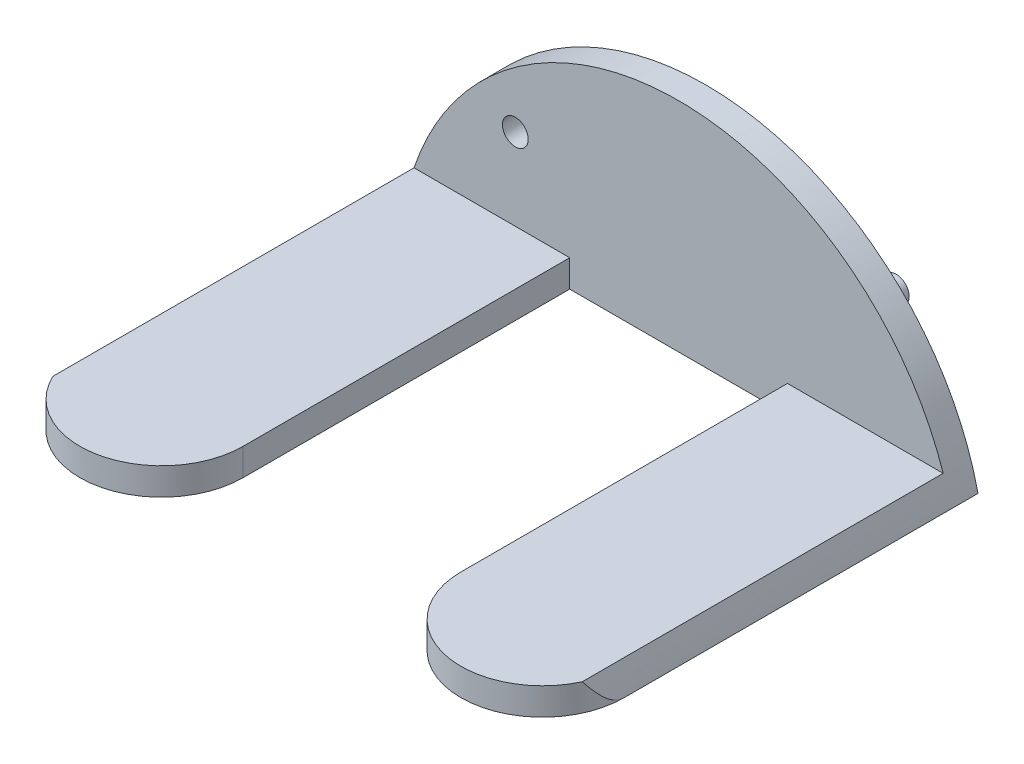
SolidWorks part; units mm, degrees
ref_plane "Front Plane" through (0, 0, 0) normal (0, 0, 1) x (1, 0, 0)
ref_plane "Top Plane" through (0, 0, 0) normal (0, 1, 0) x (1, 0, 0)
ref_plane "Right Plane" through (0, 0, 0) normal (1, 0, 0) x (0, 0, -1)
sketch "Sketch2" plane through (0, 0, 0) normal (1, 0, 0) x (0, 0, -1)
  line L0 (-50.8, 0) -> (0, 0)
  line L1 (0, 0) -> (0, 25.4)
  line L3 (-3.175, 25.4) -> (-3.175, 3.175)
  line L4 (-3.175, 3.175) -> (-50.8, 3.175)
  line L6 (-3.175, 25.4) -> (0, 25.4)
  line L7 (-50.8, 3.175) -> (-50.8, 0)
  dimension "D1" = 3.175
  dimension "D2" = 3.175
  dimension "D3" = 25.4
  dimension "D4" = 50.8
extrude "Boss-Extrude1" add sketch "Sketch2" along normal blind 63.5
sketch "Sketch3" plane through (0, 0, 0) normal (0, 0, -1) x (-1, 0, 0)
  line L0 (-50.8, 12.7) -> (-12.7, 12.7) construction
  line L1 (-63.5, 0) -> (0, 0) construction
  circle A0 centre (-50.8, 12.7) radius 1.5
  circle A1 centre (-12.7, 12.7) radius 1.5
  point P4 (-31.75, 12.7)
  point P7 (-31.75, 0)
  dimension "D3" = 3
  dimension "D1" = 12.7
  dimension "D2" = 38.1
extrude "Cut-Extrude1" cut sketch "Sketch3" against normal through all contours A1 | A1 region at (12.7, 12.7, 0)
extrude "Boss-Extrude2" add sketch "Sketch3<3>" along normal blind 3.175 contours A0 region at (50.8, 12.7, 0)
sketch "Sketch3<3>" plane through (0, 0, 0) normal (0, 0, -1) x (-1, 0, 0) same geometry as "Sketch3"
sketch "Sketch4" plane through (0, 0, 0) normal (0, 0, -1) x (-1, 0, 0)
  line L0 (-63.5, 0) -> (-63.5, 25.4)
  line L3 (-63.5, 25.4) -> (0, 25.4)
  line L4 (0, 25.4) -> (0, 0)
  line L5 (0, 0) -> (-63.5, 0)
  arc A0 (0, 0) -> (-63.5, 0) centre (-31.75, -7.1438) ccw
  line M7 (0, 0) -> (0, 25.4)
  line M9 (-63.5, 25.4) -> (-63.5, 0)
extrude "Cut-Extrude2" cut sketch "Sketch4" against normal through all contours M9 | L3 L0 | M7 | L3 L4 region at (56.285, 18.8467, 0) region at (7.215, 18.8467, 0)
sketch "Sketch5" plane through (0, 3.175, 0) normal (0, 1, 0) x (1, 0, 0)
  line L0 (0, -3.175) -> (63.5, -3.175)
  line L1 (63.5, -50.8) -> (63.5, 0) construction
  line L2 (0, -50.8) -> (0, 0) construction
  line L3 (0.8855, -3.175) -> (62.6145, -3.175) construction
  line L4 (0, -3.175) -> (0, -50.8)
  line L5 (0, -50.8) -> (63.5, -50.8)
  line L6 (63.5, -50.8) -> (63.5, -3.175)
  line L7 (0, -3.175) -> (0, -41.275)
  line L8 (19.05, -41.275) -> (19.05, -3.175)
  line L9 (63.5, -3.175) -> (63.5, -41.275)
  line L10 (44.45, -41.275) -> (44.45, -3.175)
  arc A1 (0, -41.275) -> (19.05, -41.275) centre (9.525, -41.275) ccw
  arc A2 (63.5, -41.275) -> (44.45, -41.275) centre (53.975, -41.275) cw
  line M8 (0.8855, -3.175) -> (0.8855, -50.8)
  line M9 (0.8855, -50.8) -> (62.6145, -50.8)
  line M10 (62.6145, -50.8) -> (62.6145, -3.175)
  dimension "D1" = 19.05
extrude "Cut-Extrude3" cut sketch "Sketch5" against normal blind 3.175 contours L5 A2 L10 L0 L8 A1 | A1 M8 M9 | A1 L4 L5 M8 | A2 M10 M9 | L6 A2 L5 M10 region at (0.4083, 3.175, 47.3224) region at (31.75, 3.175, 27.6638) region at (2.9015, 3.175, 49.2801) region at (60.5985, 3.175, 49.2801) region at (63.0917, 3.175, 47.3224)
